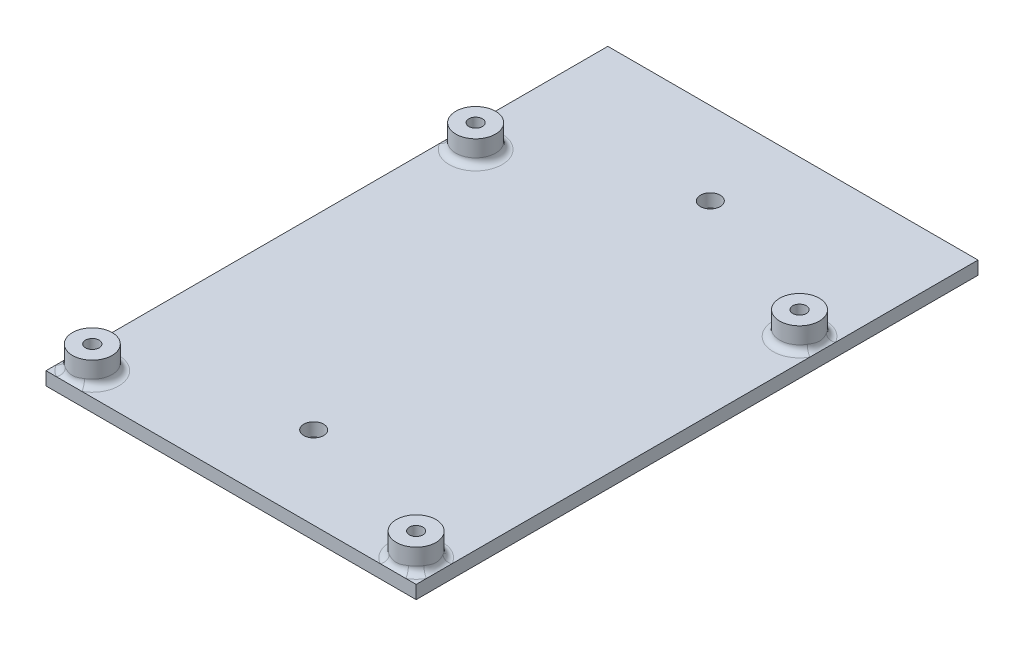
SolidWorks part; units mm, degrees
ref_plane "Front Plane" through (0, 0, 0) normal (0, 0, 1) x (1, 0, 0)
ref_plane "Top Plane" through (0, 0, 0) normal (0, 1, 0) x (1, 0, 0)
ref_plane "Right Plane" through (0, 0, 0) normal (1, 0, 0) x (0, 0, -1)
sketch "Sketch1" plane through (0, 0, 0) normal (0, 1, 0) x (1, 0, 0)
  line L1 (28, -42.5) -> (-28, -42.5)
  line L2 (28, -42.5) -> (28, 42.5)
  line L3 (28, 42.5) -> (-28, 42.5)
  line L4 (-28, -42.5) -> (-28, 42.5)
  line L5 (28, -42.5) -> (-28, 42.5) construction
  line L6 (28, 42.5) -> (-28, -42.5) construction
  circle A0 centre (-24.5, 19) radius 3
  circle A1 centre (-24.5, -39) radius 3
  circle A2 centre (24.5, -39) radius 3
  circle A3 centre (24.5, 19) radius 3
  point P0 (0, 0)
  point P6 (-24.5, -39)
  point P7 (24.5, -39)
  point P8 (24.5, 19)
  point P9 (-24.5, 19)
  dimension "D7" = 6
  dimension "D1" = 85
  dimension "D2" = 56
  dimension "D3" = 58
  dimension "D4" = 49
  dimension "D5" = 3.5
  dimension "D6" = 3.5
extrude "Boss-Extrude1" add sketch "Sketch1" against normal blind 2 contours L4 L3 L2 L1
extrude "Boss-Extrude2" add sketch "Sketch1<3>" along normal blind 3.5 contours A3 | A2 | A1 | A0 region at (24.5, 0, 39) region at (24.5, 0, -19)
sketch "Sketch1<3>" plane through (0, 0, 0) normal (0, 1, 0) x (1, 0, 0) same geometry as "Sketch1"
sketch "Sketch3" plane through (0, 3.5, 0) normal (0, 1, 0) x (1, 0, 0)
  circle A0 centre (-24.5, 19) radius 1.025
  circle A1 centre (24.5, 19) radius 1.025
  circle A2 centre (24.5, -39) radius 1.025
  circle A3 centre (-24.5, -39) radius 1.025
  dimension "D1" = 2.05
extrude "Cut-Extrude1" cut sketch "Sketch3" against normal blind 3
fillet "Fillet1" radius 1 4 edges at (-24.5, 0, 36) (24.5, 0, 36) (24.5, 0, -22) (-24.5, 0, -22)
sketch "Sketch5" plane through (0, 0, 0) normal (0, 1, 0) x (1, 0, 0)
  line L0 (0, 30) -> (0, -30) construction
  circle A0 centre (0, 30) radius 1.5
  circle A1 centre (0, -30) radius 1.5
  dimension "D2" = 3
  dimension "D1" = 60
extrude "Cut-Extrude2" cut sketch "Sketch5" against normal blind 3
